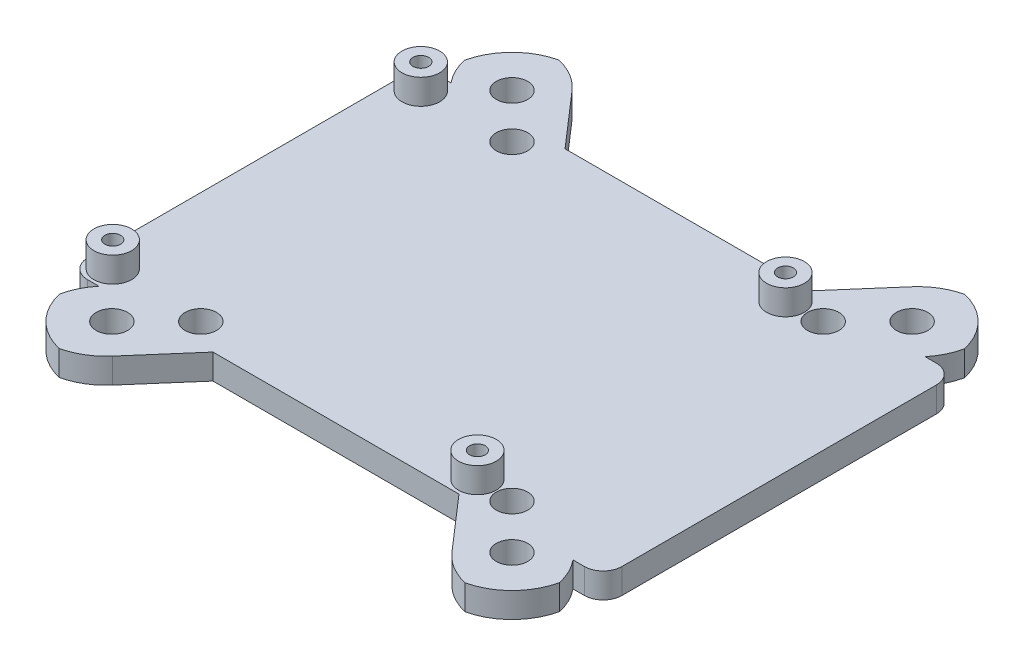
SolidWorks part; units mm, degrees
ref_plane "Front Plane" through (0, 0, 0) normal (0, 0, 1) x (1, 0, 0)
ref_plane "Top Plane" through (0, 0, 0) normal (0, 1, 0) x (1, 0, 0)
ref_plane "Right Plane" through (0, 0, 0) normal (1, 0, 0) x (0, 0, -1)
sketch "Sketch1" plane through (0, 0, 0) normal (0, 1, 0) x (1, 0, 0)
  line L1 (-42.5, -28) -> (42.5, -28)
  line L2 (-42.5, -28) -> (-42.5, 28)
  line L3 (-42.5, 28) -> (42.5, 28)
  line L4 (42.5, -28) -> (42.5, 28)
  circle A0 centre (-39, 24.5) radius 1.25
  circle A1 centre (-39, -24.5) radius 1.25
  circle A5 centre (19, 24.5) radius 1.25
  circle A6 centre (19, -24.5) radius 1.25
  point P0 (0, 0)
  dimension "D3" = 3.5
  dimension "D7" = 3.5
  dimension "D1" = 85
  dimension "D2" = 56
  dimension "D4" = 3.5
  dimension "D5" = 3.5
  dimension "D6" = 3.5
  dimension "D8" = 3.5
  dimension "D9" = 58
  dimension "D10" = 58
extrude "Boss-Extrude1" add sketch "Sketch1" along normal blind 4 contours L1 L4 L3 L2 region at (0.0414, 0, 0)
sketch "Sketch2" plane through (0, 4, 0) normal (0, 1, 0) x (1, 0, 0)
  circle A0 centre (-39, 24.5) radius 3
  circle A1 centre (19, 24.5) radius 3
  circle A2 centre (19, -24.5) radius 3
  circle A3 centre (-39, -24.5) radius 3
  circle A4 centre (-39, 24.5) radius 1.25
  circle A5 centre (19, 24.5) radius 1.25
  circle A6 centre (19, -24.5) radius 1.25
  circle A7 centre (-39, -24.5) radius 1.25
extrude "Boss-Extrude2" add sketch "Sketch2" along normal blind 4
sketch "Sketch4" plane through (0, 4, 0) normal (0, 1, 0) x (1, 0, 0)
  line L1 (-40, -40) -> (40, -40)
  line L2 (-40, -40) -> (-40, 40)
  line L3 (-40, 40) -> (40, 40)
  line L4 (40, -40) -> (40, 40)
  line L5 (-40, -40) -> (40, 40) construction
  line L6 (-40, 40) -> (40, -40) construction
  point P0 (0, 0)
  dimension "D1" = 80
  dimension "D2" = 80
fillet "Fillet1" radius 3 4 edges at (42.5, 2, -28) (42.5, 2, 28) (-42.5, 2, 28) (-42.5, 2, -28)
sketch "Sketch5" plane through (0, 0, 0) normal (0, 1, 0) x (1, 0, 0)
  line L1 (15, -15) -> (-15, -15) construction
  line L2 (15, -15) -> (15, 15) construction
  line L3 (15, 15) -> (-15, 15) construction
  line L4 (-15, -15) -> (-15, 15) construction
  line L5 (15, -15) -> (-15, 15) construction
  line L6 (15, 15) -> (-15, -15) construction
  line L11 (-40, -30) -> (-17, -10)
  line L13 (-17, -10) -> (-17, 10)
  line L14 (-17, 10) -> (-40, 30)
  line L18 (10, 17) -> (30, 40)
  line L19 (-10, 17) -> (10, 17)
  line L20 (-30, 40) -> (-10, 17)
  line L22 (17, -10) -> (40, -30)
  line L23 (17, 10) -> (17, -10)
  line L24 (40, 30) -> (17, 10)
  line L26 (-10, -17) -> (-30, -40)
  line L27 (10, -17) -> (-10, -17)
  line L28 (30, -40) -> (10, -17)
  line L29 (-40, 30) -> (-40, 40)
  line L30 (-40, 40) -> (-30, 40)
  line L31 (30, 40) -> (40, 40)
  line L32 (40, 40) -> (40, 30)
  line L33 (40, -30) -> (40, -40)
  line L34 (40, -40) -> (30, -40)
  line L35 (-30, -40) -> (-40, -40)
  line L36 (-40, -40) -> (-40, -30)
  point P0 (0, 0)
  point P6 (-40, 0)
  point P32 (0, 0)
  dimension "D1" = 30
  dimension "D2" = 30
  dimension "D7" = 4
extrude "Boss-Extrude4" add sketch "Sketch5" along normal blind 4
sketch "Sketch3" plane through (0, 4, 0) normal (0, 1, 0) x (1, 0, 0)
  line L1 (-31.8198, -31.8198) -> (31.8198, -31.8198) construction
  line L2 (-31.8198, -31.8198) -> (-31.8198, 31.8198) construction
  line L3 (-31.8198, 31.8198) -> (31.8198, 31.8198) construction
  line L4 (31.8198, -31.8198) -> (31.8198, 31.8198) construction
  line L5 (-31.8198, -31.8198) -> (31.8198, 31.8198) construction
  line L6 (-31.8198, 31.8198) -> (31.8198, -31.8198) construction
  line L7 (-24.7487, -24.7487) -> (24.7487, -24.7487) construction
  line L8 (-24.7487, -24.7487) -> (-24.7487, 24.7487) construction
  line L9 (-24.7487, 24.7487) -> (24.7487, 24.7487) construction
  line L10 (24.7487, -24.7487) -> (24.7487, 24.7487) construction
  line L11 (-24.7487, -24.7487) -> (24.7487, 24.7487) construction
  line L12 (-24.7487, 24.7487) -> (24.7487, -24.7487) construction
  circle A0 centre (-31.8198, 31.8198) radius 2.5
  circle A1 centre (-24.7487, 24.7487) radius 2.5
  circle A2 centre (31.8198, 31.8198) radius 2.5
  circle A3 centre (24.7487, 24.7487) radius 2.5
  circle A4 centre (24.7487, -24.7487) radius 2.5
  circle A5 centre (31.8198, -31.8198) radius 2.5
  circle A6 centre (-31.8198, -31.8198) radius 2.5
  circle A7 centre (-24.7487, -24.7487) radius 2.5
  point P0 (0, 0)
  point P6 (0, 0)
  dimension "D1" = 35
  dimension "D2" = 45
extrude "Cut-Extrude1" cut sketch "Sketch3" against normal through all
fillet "Fillet2" radius 10 12 edges at (-40, 2, -30) (-40, 2, -40) (-30, 2, -40) (30, 2, -40) (40, 2, -40) (40, 2, -30) (40, 2, 30) (40, 2, 40) (30, 2, 40) (-40, 2, 30) (-30, 2, 40) (-40, 2, 40)
